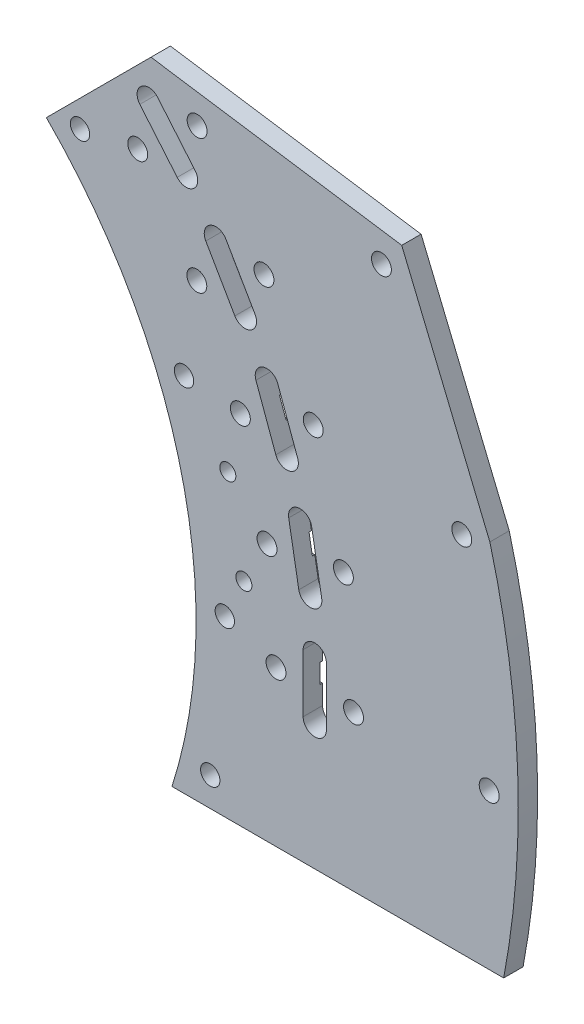
SolidWorks part; units mm, degrees
ref_plane "Front Plane" through (0, 0, 0) normal (0, 0, 1) x (1, 0, 0)
ref_plane "Top Plane" through (0, 0, 0) normal (0, 1, 0) x (1, 0, 0)
ref_plane "Right Plane" through (0, 0, 0) normal (1, 0, 0) x (0, 0, -1)
sketch "Sketch1" plane through (0, 0, 0) normal (0, 0, 1) x (1, 0, 0)
  line L0 (0, 0) -> (177.8, 0) construction
  line L1 (176.8984, 6.1774) -> (0, 0) construction
  line L2 (0, 0) -> (121.7947, 121.7947) construction
  line L3 (121.7947, 121.7947) -> (122.9173, 122.9173) construction
  line L4 (129.4542, 120.718) -> (0, 0) construction
  line L5 (0, 0) -> (163.5325, 67.7374) construction
  line L6 (167.4812, 0) -> (167.4812, -50.8) construction
  line L8 (159.5911, -50.8) -> (167.4812, -50.8) construction
  line L9 (172.1267, -41.275) -> (0, 0) construction
  line L10 (159.5911, -50.8) -> (268.2828, -50.8)
  line L11 (118.4271, 118.4271) -> (152.7152, 152.7152)
  line L12 (177.8, 0) -> (193.675, 0) construction
  line L13 (202.565, 0) -> (210.185, 0) construction
  line L14 (210.185, 0) -> (219.075, 0) construction
  line L15 (193.675, 0) -> (202.565, 0) construction
  line L16 (202.565, 0) -> (202.565, 9.525)
  line L17 (202.565, 0) -> (202.565, -9.525)
  line L18 (210.185, 9.525) -> (210.185, 0)
  line L19 (210.185, 0) -> (210.185, -9.525)
  line L20 (202.565, -9.525) -> (210.185, -9.525) construction
  line L21 (202.565, 9.525) -> (210.185, 9.525) construction
  line L22 (210.185, 9.525) -> (219.075, 0) construction
  line L23 (202.565, 9.525) -> (193.675, 0) construction
  line L24 (199.4876, 35.175) -> (201.1416, 25.7947)
  line L25 (199.4876, 35.175) -> (197.8336, 44.5553)
  line L26 (205.3378, 45.8785) -> (206.9918, 36.4982)
  line L27 (206.9918, 36.4982) -> (208.6458, 27.1179)
  line L28 (190.3488, 69.2813) -> (193.6066, 60.3307)
  line L29 (190.3488, 69.2813) -> (187.0911, 78.2319)
  line L30 (194.2516, 80.8381) -> (197.5093, 71.8875)
  line L31 (197.5093, 71.8875) -> (200.767, 62.9369)
  line L32 (175.4264, 101.2825) -> (180.1889, 93.0336)
  line L33 (175.4264, 101.2825) -> (170.6639, 109.5314)
  line L34 (177.263, 113.3414) -> (182.0255, 105.0925)
  line L35 (182.0255, 105.0925) -> (186.788, 96.8436)
  line L36 (155.1738, 130.2063) -> (161.2963, 122.9097)
  line L37 (155.1738, 130.2063) -> (149.0512, 137.5028)
  line L38 (154.8885, 142.4009) -> (161.0111, 135.1043)
  line L39 (161.0111, 135.1043) -> (167.1336, 127.8077)
  line L40 (0, 0) -> (193.675, 0) construction
  line L41 (0, 0) -> (190.7326, 33.6313) construction
  line L42 (0, 0) -> (254, 0) construction
  line L43 (254, 0) -> (263.525, 0) construction
  line L44 (254.5456, 68.2053) -> (0, 0) construction
  line L45 (152.7152, 152.7152) -> (234.123, 140.5088)
  line L46 (167.8212, 140.8187) -> (228.2193, 131.7625) construction
  line L47 (254.5456, 68.2053) -> (263.746, 70.6705) construction
  line L48 (0, 0) -> (183.1412, 19.2489) construction
  line L49 (228.2193, 131.7625) -> (254.5456, 68.2053) construction
  line L51 (263.746, 70.6705) -> (234.8641, 140.3976)
  line L52 (234.123, 140.5088) -> (234.8641, 140.3976)
  arc A0 (172.2437, 0) -> (121.7947, 121.7947) centre (0, 0) ccw construction
  arc A1 (173.8312, 0) -> (122.9173, 122.9173) centre (0, 0) ccw construction
  circle A2 centre (176.8984, 6.1774) radius 3.175
  circle A3 centre (129.4542, 120.718) radius 3.175
  circle A4 centre (163.5325, 67.7374) radius 3.175
  arc A5 (167.4812, 0) -> (118.4271, 118.4271) centre (0, 0) ccw
  arc A6 (167.4812, 0) -> (159.5911, -50.8) centre (0, 0) cw
  arc A7 (173.8312, 0) -> (166.2428, -50.8) centre (0, 0) cw construction
  circle A8 centre (172.1267, -41.275) radius 3.175
  circle A9 centre (193.675, 0) radius 9.525 construction
  circle A10 centre (219.075, 0) radius 9.525 construction
  arc A11 (202.565, -9.525) -> (210.185, -9.525) centre (206.375, -9.525) ccw
  arc A12 (202.565, 9.525) -> (210.185, 9.525) centre (206.375, 9.525) cw
  circle A13 centre (193.675, 0) radius 3.2639
  circle A14 centre (219.075, 0) radius 3.2639
  circle A15 centre (215.7468, 38.042) radius 3.2639
  arc A16 (201.1416, 25.7947) -> (208.6458, 27.1179) centre (204.8937, 26.4563) ccw
  arc A17 (197.8336, 44.5553) -> (205.3378, 45.8785) centre (201.5857, 45.2169) cw
  circle A18 centre (190.7326, 33.6313) radius 3.2639
  circle A19 centre (205.8632, 74.9281) radius 3.2639
  arc A20 (193.6066, 60.3307) -> (200.767, 62.9369) centre (197.1868, 61.6338) ccw
  arc A21 (187.0911, 78.2319) -> (194.2516, 80.8381) centre (190.6713, 79.535) cw
  circle A22 centre (181.995, 66.2408) radius 3.2639
  circle A23 centre (189.7245, 109.5375) radius 3.2639
  arc A24 (180.1889, 93.0336) -> (186.788, 96.8436) centre (183.4885, 94.9386) ccw
  arc A25 (170.6639, 109.5314) -> (177.263, 113.3414) centre (173.9635, 111.4364) cw
  circle A26 centre (167.7275, 96.8375) radius 3.2639
  circle A27 centre (167.8212, 140.8187) radius 3.2639
  arc A28 (161.2963, 122.9097) -> (167.1336, 127.8077) centre (164.215, 125.3587) ccw
  arc A29 (149.0512, 137.5028) -> (154.8885, 142.4009) centre (151.9699, 139.9519) cw
  circle A30 centre (148.3637, 124.4919) radius 3.2639
  circle A31 centre (263.525, 0) radius 3.2639
  circle A32 centre (254.5456, 68.2053) radius 3.2639
  circle A33 centre (228.2193, 131.7625) radius 3.2639
  arc A34 (263.746, 70.6705) -> (268.2828, -50.8) centre (0, 0) cw
  circle A35 centre (177.8752, 47.6615) radius 2.6289
  circle A36 centre (183.1412, 19.2489) radius 2.6289
  arc A37 (234.123, 140.5088) -> (263.746, 70.6705) centre (0, 0) cw construction
  point P3 (172.2437, 0)
  point P96 (0, 0)
  dimension "D3" = 1.5875
  dimension "D4" = 6.35
  dimension "D5" = 2
  dimension "D7" = 2
  dimension "D8" = 6.35
  dimension "D9" = 6.35
  dimension "D11" = 6.35
  dimension "D13" = 6.35
  dimension "D15" = 19.05
  dimension "D16" = 7.62
  dimension "D17" = 19.05
  dimension "D21" = 15.875
  dimension "D22" = 6.5278
  dimension "D23" = 6.5278
  dimension "D28" = 6.5278
  dimension "D32" = 9.525
  dimension "D33" = 184.15
  dimension "D34" = 5.2578
  dimension "D36" = 5.2578
  dimension "D1" = 177.8
  dimension "D2" = 5.5562
  dimension "D6" = 45
  dimension "D10" = 22.5
  dimension "D12" = 50.8
  dimension "D14" = 9.525
  dimension "D18" = 9.525
  dimension "D19" = 9.525
  dimension "D20" = 25.4
  dimension "D25" = 10
  dimension "D26" = 254
  dimension "D27" = 9.525
  dimension "D30" = 15
  dimension "D31" = 9.525
  dimension "D35" = 6
  dimension "D37" = 184.15
  dimension "D24" = 5
  dimension "D29" = 3
extrude "Boss-Extrude1" add sketch "Sketch1" along normal blind 6.35 contours A34 L45 L11 A5 A6 L10 A33 A32 A31 A30 A27 A26 A23 A22 A19 A18 A15 A14 A13 A8 A4 A3 A2 L16 A12 L18 L19 A11 L17 L25 A17 L26 region at (207.9288, 47.7641, 0)
sketch "Sketch2" plane through (0, 0, 0) normal (0, 0, 1) x (1, 0, 0)
  line L0 (202.565, -9.525) -> (202.565, 9.525) construction
  line L1 (210.185, 9.525) -> (210.185, -9.525) construction
  line L2 (0, 0) -> (202.565, 0) construction
  line L3 (0, 0) -> (199.4876, 35.175) construction
  circle A0 centre (202.565, 0) radius 3.175
  circle A1 centre (210.185, 0) radius 3.175
  circle A2 centre (199.4876, 35.175) radius 3.175
  circle A3 centre (206.9918, 36.4982) radius 3.175
  circle A4 centre (190.3488, 69.2813) radius 3.175
  circle A5 centre (197.5093, 71.8875) radius 3.175
  circle A6 centre (175.4264, 101.2825) radius 3.175
  circle A7 centre (182.0255, 105.0925) radius 3.175
  circle A8 centre (155.1738, 130.2063) radius 3.175
  circle A9 centre (161.0111, 135.1043) radius 3.175
  dimension "D1" = 6.35
  dimension "D2" = 6.35
  dimension "D4" = 10
  dimension "D3" = 5
extrude "Cut-Extrude1" cut sketch "Sketch2" along normal blind 0.7937
